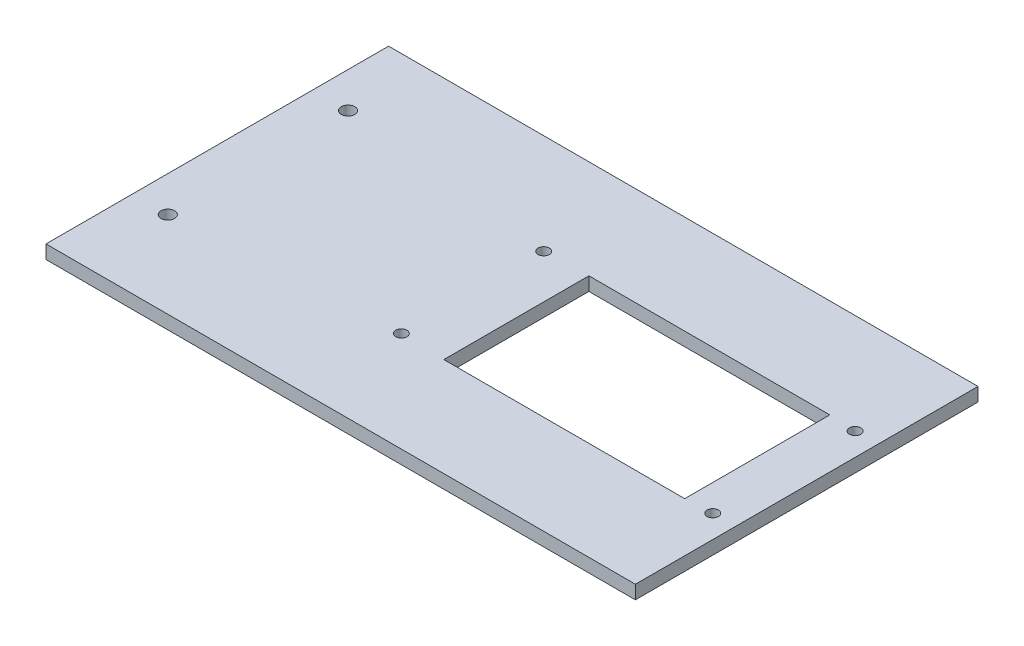
SolidWorks part; units mm, degrees
ref_plane "Front" through (0, 0, 0) normal (0, 0, 1) x (1, 0, 0)
ref_plane "Top" through (0, 0, 0) normal (0, 1, 0) x (1, 0, 0)
ref_plane "Right" through (0, 0, 0) normal (1, 0, 0) x (0, 0, -1)
sketch "Sketch1" plane through (0, 0, 0) normal (0, 1, 0) x (1, 0, 0)
  line L1 (0, 0) -> (130.41, 0)
  line L2 (0, 0) -> (0, -75.8)
  line L3 (0, -75.8) -> (130.41, -75.8)
  line L4 (130.41, 0) -> (130.41, -75.8)
  line L5 (66.17, -21.85) -> (119.47, -21.85)
  line L6 (54.17, -19.15) -> (127.67, -19.15)
  line L7 (54.17, -19.15) -> (54.17, -56.65)
  line L8 (54.17, -56.65) -> (127.67, -56.65)
  line L9 (127.67, -19.15) -> (127.67, -56.65)
  line L10 (123.42, -31.15) -> (125.92, -31.15)
  line L11 (123.42, -31.15) -> (123.42, -46.15)
  line L12 (123.42, -46.15) -> (125.92, -46.15)
  line L13 (125.92, -31.15) -> (125.92, -46.15)
  line L14 (58.17, -19.15) -> (122.27, -19.15)
  line L15 (58.17, -19.15) -> (58.17, -56.65)
  line L16 (58.17, -56.65) -> (122.27, -56.65)
  line L17 (122.27, -19.15) -> (122.27, -56.65)
  line L18 (66.17, -21.85) -> (66.17, -53.95)
  line L19 (66.17, -53.95) -> (119.47, -53.95)
  line L20 (119.47, -21.85) -> (119.47, -53.95)
  circle A0 centre (56.47, -22.15) radius 1.25
  circle A1 centre (125.37, -22.15) radius 1.25
  circle A2 centre (125.37, -53.65) radius 1.25
  circle A3 centre (56.47, -53.65) radius 1.25
  point P21 (124.67, -31.15)
  point P22 (124.67, -46.15)
  point P27 (122.27, -37.9)
  dimension "D5" = 2.5
  dimension "D8" = 2.5
  dimension "D11" = 2.5
  dimension "D14" = 2.5
  dimension "D1" = 130.41
  dimension "D2" = 75.8
  dimension "D3" = 37.5
  dimension "D4" = 73.5
  dimension "D6" = 3
  dimension "D7" = 2.3
  dimension "D9" = 3
  dimension "D10" = 2.3
  dimension "D12" = 3
  dimension "D13" = 2.3
  dimension "D15" = 3
  dimension "D16" = 2.3
  dimension "D17" = 2.5
  dimension "D18" = 15
  dimension "D19" = 12
  dimension "D20" = 3
  dimension "D21" = 37.5
  dimension "D22" = 64.1
  dimension "D23" = 5.4
  dimension "D24" = 53.3
  dimension "D25" = 2.7
  dimension "D26" = 2.7
  dimension "D27" = 8.2
  dimension "D28" = 2.74
  dimension "D29" = 19.15
extrude "Boss-Extrude1" add sketch "Sketch1" along normal blind 3 contours L2 L3 L4 L1
extrude "Cut-Extrude2" cut sketch "Sketch1<4>" along normal through all contours L5 L20 L19 L18
sketch "Sketch1<4>" plane through (0, 0, 0) normal (0, 1, 0) x (1, 0, 0) same geometry as "Sketch1"
extrude "Cut-Extrude3" cut sketch "Sketch1<5>" along normal through all contours A3 | A0 | A1 | A2 region at (56.47, 0, 53.65)
sketch "Sketch1<5>" plane through (0, 0, 0) normal (0, 1, 0) x (1, 0, 0) same geometry as "Sketch1"
sketch "Sketch2" plane through (0, 3, 0) normal (0, 1, 0) x (1, 0, 0)
  line L0 (0, 0) -> (0, -75.8) construction
  line L1 (0, 0) -> (130.41, 0) construction
  circle A0 centre (7.86, -16.83) radius 1.5
  dimension "D1" = 3
  dimension "D2" = 7.86
  dimension "D3" = 16.83
extrude "Cut-Extrude4" cut sketch "Sketch2" against normal through all
sketch "Sketch3" plane through (0, 3, 0) normal (0, 1, 0) x (1, 0, 0)
  line L0 (0, 0) -> (0, -75.8) construction
  circle A0 centre (7.86, -56.71) radius 1.5
  circle A1 centre (7.86, -16.83) radius 1.5 construction
  dimension "D1" = 3
  dimension "D2" = 39.88
  dimension "D3" = 7.86
extrude "Cut-Extrude5" cut sketch "Sketch3" against normal through all
